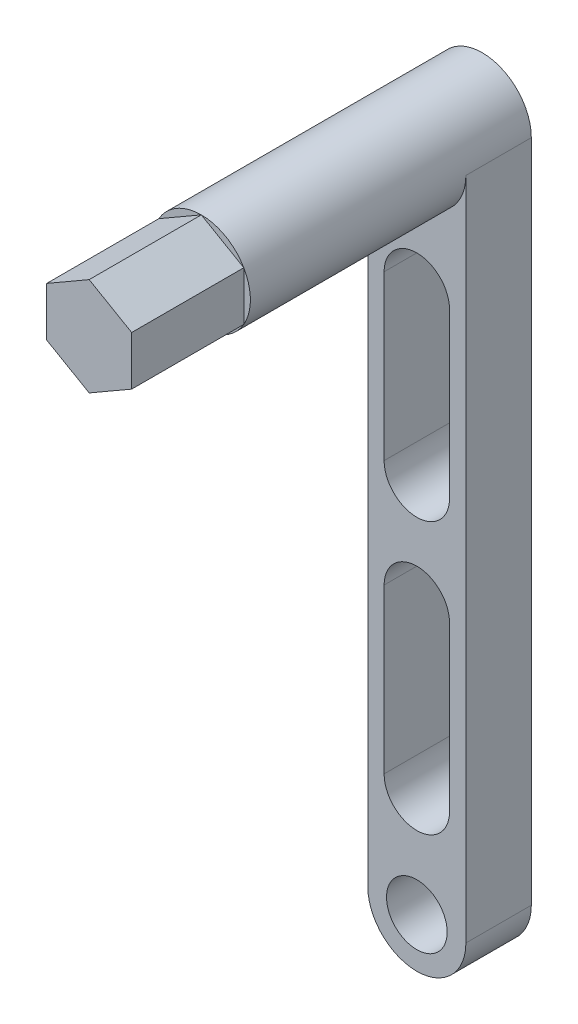
SolidWorks part; units mm, degrees
material "PEI"
ref_plane "Front Plane" through (0, 0, 0) normal (0, 0, 1) x (1, 0, 0)
ref_plane "Top Plane" through (0, 0, 0) normal (0, 1, 0) x (1, 0, 0)
ref_plane "Right Plane" through (0, 0, 0) normal (1, 0, 0) x (0, 0, -1)
sketch "Sketch1" plane through (0, 0, 0) normal (0, 0, 1) x (1, 0, 0)
  line L0 (0, -50.8) -> (0, 50.8) construction
  line L1 (-7.5, -50.8) -> (-7.5, 50.8)
  line L2 (7.5, -50.8) -> (7.5, 50.8)
  line L3 (0, -34.665) -> (0, -9.665) construction
  line L4 (-5, -34.665) -> (-5, -9.665)
  line L5 (5, -34.665) -> (5, -9.665)
  line L6 (0, 31.8) -> (0, 6.8) construction
  line L7 (5, 31.8) -> (5, 6.8)
  line L8 (-5, 31.8) -> (-5, 6.8)
  line L9 (-5, 19.3) -> (5, 19.3) construction
  line L10 (-5, -22.165) -> (5, -22.165) construction
  line L12 (0, 58.3) -> (0, 36.8) construction
  arc A0 (-7.5, -50.8) -> (7.5, -50.8) centre (0, -50.8) ccw
  arc A1 (7.5, 50.8) -> (-7.5, 50.8) centre (0, 50.8) ccw
  circle A2 centre (0, -50.8) radius 4.635
  arc A4 (-5, -34.665) -> (5, -34.665) centre (0, -34.665) ccw
  arc A5 (5, -9.665) -> (-5, -9.665) centre (0, -9.665) ccw
  arc A6 (5, 31.8) -> (-5, 31.8) centre (0, 31.8) ccw
  arc A7 (-5, 6.8) -> (5, 6.8) centre (0, 6.8) ccw
  circle A8 centre (0, 50.8) radius 7.5
  point P2 (0, 0)
  point P14 (0, -22.165)
  point P19 (0, 19.3)
  point P30 (0, -4.665)
  point P32 (0, -46.165)
  point P33 (0, -39.665)
  point P35 (0, 1.8)
  point P37 (0, 43.3)
  dimension "D3" = 9.27
  dimension "D1" = 101.6
  dimension "D2" = 15
  dimension "D4" = 10
  dimension "D5" = 6.5
  dimension "20" = 25
  dimension "D6" = 6.5
extrude "Boss-Extrude1" add sketch "Sketch1" along normal blind 10 contours A8 L1 A0 L2 A7 L8 A6 L7 A5 L5 A4 L4 A2 region at (-6.3987, 0, 0)
extrude "Boss-Extrude2" add sketch "Sketch1<4>" along normal blind 42.94 contours A1 A8 region at (0, 50.8, 0)
sketch "Sketch1<4>" plane through (0, 0, 0) normal (0, 0, 1) x (1, 0, 0) same geometry as "Sketch1"
sketch "Sketch2" plane through (0, 0, 42.94) normal (0, 0, 1) x (1, 0, 0)
  point P0 (0, 50.8)
  point P1 (0, 0)
sketch "Sketch3" plane through (0, 0, 42.94) normal (0, 0, 1) x (1, 0, 0)
  line L1 (0, 43.3) -> (6.4952, 47.05)
  line L2 (6.4952, 47.05) -> (6.4952, 54.55)
  line L3 (6.4952, 54.55) -> (0, 58.3)
  line L4 (0, 58.3) -> (-6.4952, 54.55)
  line L5 (-6.4952, 54.55) -> (-6.4952, 47.05)
  line L6 (-6.4952, 47.05) -> (0, 43.3)
  circle A0 centre (0, 50.8) radius 6.4952 construction
extrude "Boss-Extrude3" add sketch "Sketch3" along normal blind 17.14
